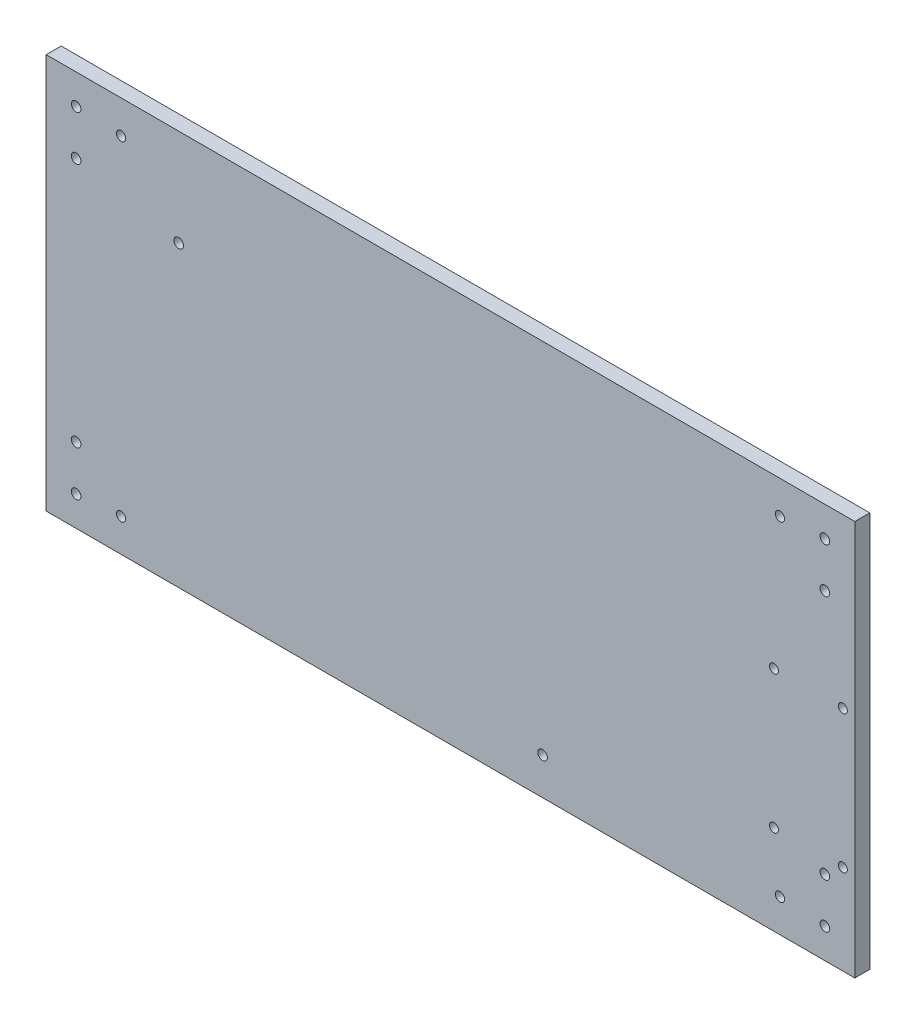
SolidWorks part; units mm, degrees
ref_plane "Front Plane" through (0, 0, 0) normal (0, 0, 1) x (1, 0, 0)
ref_plane "Top Plane" through (0, 0, 0) normal (0, 1, 0) x (1, 0, 0)
ref_plane "Right Plane" through (0, 0, 0) normal (1, 0, 0) x (0, 0, -1)
sketch "Sketch1" plane through (0, 0, 0) normal (0, 0, 1) x (1, 0, 0)
  line L1 (135, -66) -> (-135, -66)
  line L2 (135, -66) -> (135, 66)
  line L3 (135, 66) -> (-135, 66)
  line L4 (-135, -66) -> (-135, 66)
  line L5 (135, -66) -> (-135, 66) construction
  line L6 (135, 66) -> (-135, -66) construction
  point P0 (0, 0)
  dimension "D1" = 270
  dimension "D2" = 132
extrude "Base" add sketch "Sketch1" along normal mid plane 5 contours L4 L1 L2 L3 region at (0, 0, 0)
sketch "Sketch3" plane through (0, 0, -2.5) normal (0, 0, -1) x (-1, 0, 0)
  line L3 (90.75, -53.65) -> (-30.75, -53.65) construction
  line L4 (90.75, -53.65) -> (90.75, 33.65) construction
  line L5 (90.75, 33.65) -> (-30.75, 33.65) construction
  line L6 (-30.75, -53.65) -> (-30.75, 33.65) construction
  line L7 (90.75, -53.65) -> (-30.75, 33.65) construction
  line L8 (90.75, 33.65) -> (-30.75, -53.65) construction
  circle A0 centre (-30.75, -53.65) radius 1.6
  circle A1 centre (90.75, 33.65) radius 1.6
  point P2 (30, -10)
  dimension "D3" = 3.2
  dimension "D1" = 121.5
  dimension "D2" = 87.3
  dimension "D4" = 10
  dimension "D5" = 30
extrude "PSUMount" cut sketch "Sketch3" against normal through all
sketch "Sketch4" plane through (0, 0, 2.5) normal (0, 0, 1) x (1, 0, 0)
  line L1 (131, 10) -> (108, 10) construction
  line L2 (131, 10) -> (131, -36) construction
  line L3 (131, -36) -> (108, -36) construction
  line L4 (108, 10) -> (108, -36) construction
  line L5 (131, 10) -> (108, -36) construction
  line L6 (131, -36) -> (108, 10) construction
  line L7 (135, -66) -> (135, 66) construction
  circle A0 centre (108, 10) radius 1.5
  circle A1 centre (131, 10) radius 1.5
  circle A2 centre (108, -36) radius 1.5
  circle A3 centre (131, -36) radius 1.5
  point P0 (119.5, -13)
  point P16 (135, 0)
  dimension "D5" = 3
  dimension "D1" = 46
  dimension "D2" = 23
  dimension "D3" = 4
  dimension "D4" = 13
extrude "InterfaceHoles" cut sketch "Sketch4" against normal through all
sketch "Sketch5" plane through (0, 0, 2.5) normal (0, 0, 1) x (1, 0, 0)
  line L1 (110, -55) -> (-110, -55) construction
  line L2 (110, -55) -> (110, 55) construction
  line L3 (110, 55) -> (-110, 55) construction
  line L4 (-110, -55) -> (-110, 55) construction
  line L5 (110, -55) -> (-110, 55) construction
  line L6 (110, 55) -> (-110, -55) construction
  circle A0 centre (-110, -55) radius 1.55
  circle A1 centre (-110, 55) radius 1.55
  circle A2 centre (110, 55) radius 1.55
  circle A3 centre (110, -55) radius 1.55
  point P8 (0, 0)
  dimension "D1" = 3.1
  dimension "D2" = 110
  dimension "D3" = 220
extrude "Cut-Extrude2" cut sketch "Sketch5" against normal through all
hole_wizard "Ø3.2 (3.2) WallMountHoles" positions "Sketch6" profile "Sketch7" hole size "Ø3.2" standard "ANSI Metric" end condition through all
sketch "Sketch6" plane through (0, 0, 2.5) normal (0, 0, 1) x (1, 0, 0)
  line L0 (135, 66) -> (-135, 66) construction
  line L1 (-135, -66) -> (-135, 66) construction
  line L4 (135, -66) -> (135, 66) construction
  line L5 (135, -66) -> (-135, -66) construction
  point P0 (-125, 56)
  point P2 (-125, 41)
  point P4 (-125, -41)
  point P6 (-125, -56)
  point P8 (125, -56)
  point P10 (125, -41)
  point P12 (125, 41)
  point P14 (125, 56)
  point P21 (0, 0)
  point P22 (0, 0)
  point P23 (0, 0)
  point P24 (0, 0)
  point P25 (0, 0)
  point P26 (0, 0)
  point P27 (0, 0)
  point P28 (0, 0)
  point P31 (115.1931, 51)
  point P34 (0, 0)
  point P35 (-125, -35.3297)
  point P36 (-125, -54.5644)
  point P37 (117.0945, -34.6112)
  point P38 (102.7762, -54.7814)
  point P39 (0, 0)
  point P40 (122.8933, 56)
  dimension "D1" = 10
  dimension "D2" = 25
  dimension "D4" = 10
  dimension "D3" = 10
  dimension "D5" = 10
  dimension "D6" = 25
sketch "Sketch7" plane through (-125, 56, 2.5) normal (1, 0, 0) x (0, -1, 0)
  line L0 (0, 0) -> (0, 5)
  line L1 (0, 5) -> (1.6, 5)
  line L2 (1.6, 5) -> (1.6, 0)
  line L5 (1.6, 0) -> (0, 0)
  line L11 (0, -6.35) -> (0, 107.95) construction
  dimension "Thru Hole Dia." = 3.2
  dimension "Thru Hole Depth" = 5
equation "\"D3@Sketch6\"=\"D4@Sketch6\""
equation "\"D5@Sketch6\"=\"D1@Sketch6\""
equation "\"D6@Sketch6\"=\"D2@Sketch6\""
